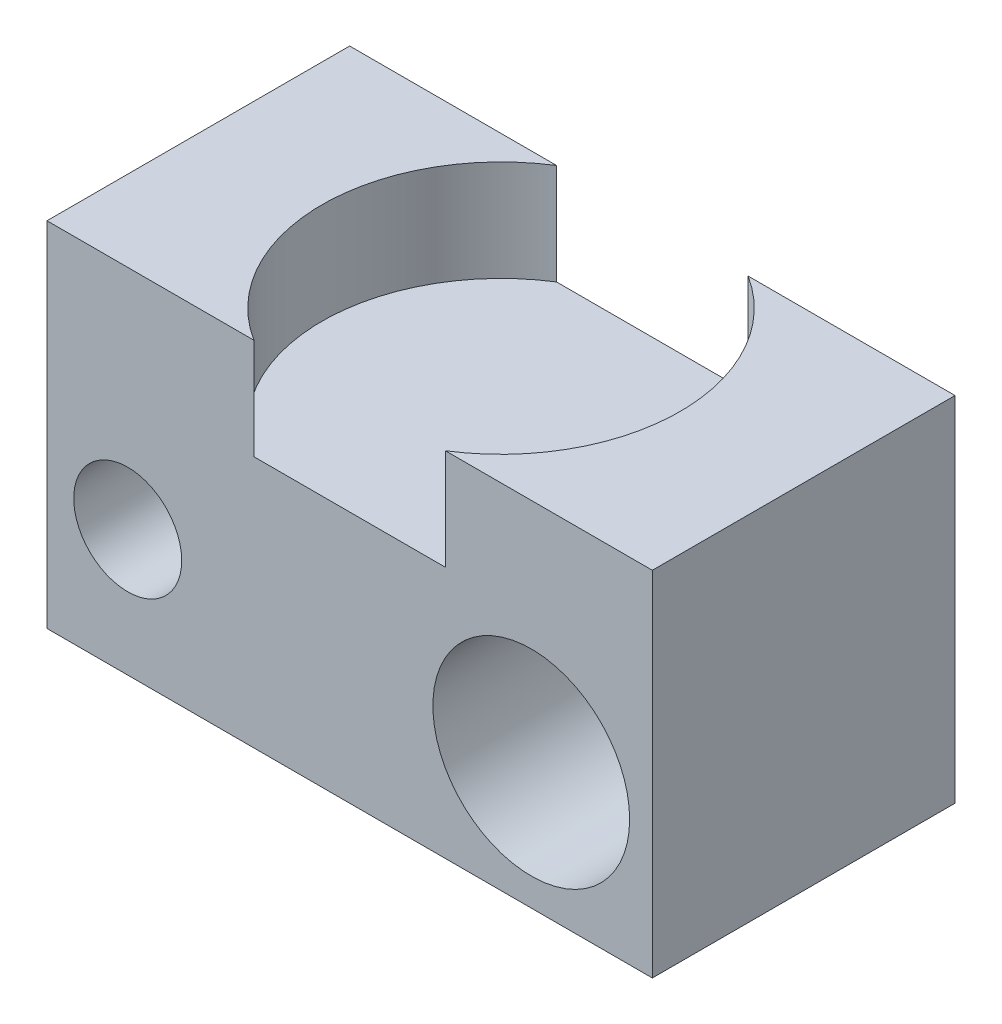
SolidWorks part; units mm, degrees
ref_plane "Front Plane" through (0, 0, 0) normal (0, 0, 1) x (1, 0, 0)
ref_plane "Top Plane" through (0, 0, 0) normal (0, 1, 0) x (1, 0, 0)
ref_plane "Right Plane" through (0, 0, 0) normal (1, 0, 0) x (0, 0, -1)
sketch "Sketch1" plane through (0, 0, 0) normal (0, 0, 1) x (1, 0, 0)
  line L1 (-30, -12.5) -> (30, -12.5)
  line L2 (-30, -12.5) -> (-30, 12.5)
  line L3 (-30, 12.5) -> (30, 12.5)
  line L4 (30, -12.5) -> (30, 12.5)
  line L5 (-30, -12.5) -> (30, 12.5) construction
  line L6 (-30, 12.5) -> (30, -12.5) construction
  circle A0 centre (18, 0) radius 9.75
  circle A1 centre (-22, 0) radius 5.35
  point P0 (0, 0)
  dimension "D2" = 10.7
  dimension "D3" = 19.5
  dimension "D5" = 8
  dimension "D7" = 12.5
  dimension "D1" = 40
  dimension "D4" = 12
  dimension "D6" = 25
  dimension "D8" = 0
extrude "Boss-Extrude1" add sketch "Sketch1" along normal blind 30
sketch "Sketch2" plane through (0, 12.5, 0) normal (0, 1, 0) x (1, 0, 0)
  circle A0 centre (0, -15) radius 17.75
  line M1 (30, 0) -> (-30, 0)
  line M2 (-30, 0) -> (-30, -30)
  line M3 (-30, -30) -> (30, -30)
  line M4 (30, -30) -> (30, 0)
  dimension "36" = 35.5
extrude "Boss-Extrude2" add sketch "Sketch2" along normal blind 10 contours A0 M1 M2 M3 | A0 M3 M4 M1 region at (22.4736, 12.5, 15) region at (-22.4736, 12.5, 15)
